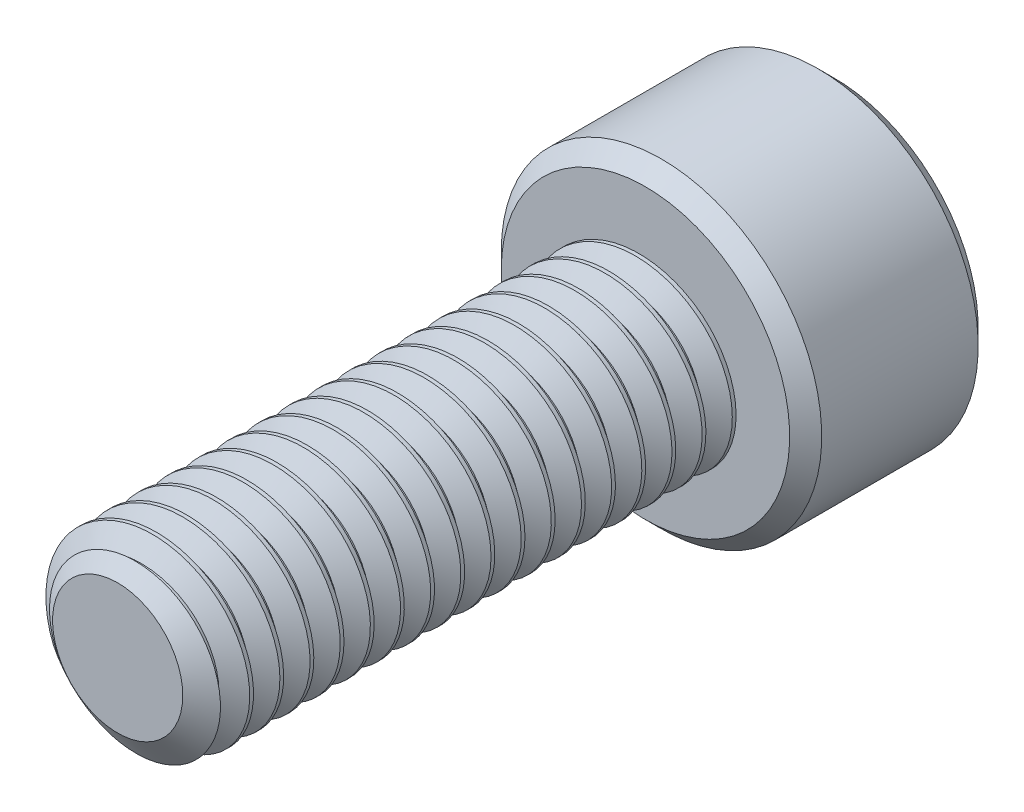
SolidWorks part; units mm, degrees
note: '?' marks a value the reader was unsure of.
other "DetailItem1"
ref_plane "Front Plane" through (0, 0, 0) normal (0, 0, 1) x (1, 0, 0)
ref_plane "Top Plane" through (0, 0, 0) normal (0, 1, 0) x (1, 0, 0)
ref_plane "Right Plane" through (0, 0, 0) normal (1, 0, 0) x (0, 0, -1)
sketch "Sketch1" plane through (0, 0, 0) normal (0, 0, 1) x (1, 0, 0)
  circle A0 centre (0, 0) radius 2.5
  dimension "OD" = 5
extrude "Extrude1" add sketch "Sketch1" against normal blind 14
sketch "Sketch2" plane through (0, 0, 0) normal (0, 0, 1) x (1, 0, 0)
  circle A0 centre (0, 0) radius 2.5 construction
  circle A1 centre (0, 0) radius 2.5
curve "Helix/Spiral1" pitch 0.8 height 14.8 turns 18.5 parameters "pitch"=0.8
sketch "Sketch3" plane through (0, 0, 0) normal (1, 0, 0) x (0, 0, -1)
  line L0 (-0.7, 2.5) -> (-0.4, 1.9804)
  line L1 (-0.4, 1.9804) -> (-0.3, 1.9804)
  line L2 (-0.3, 1.9804) -> (0, 2.5)
  line L3 (-0.7, 2.5) -> (0, 2.5)
  line L4 (-0.35, 2.5) -> (-0.35, 1.9804) construction
  line L5 (-0.55, 2.2402) -> (-0.15, 2.2402) construction
  line L6 (0, 2.5) -> (0, -2.5) construction
  dimension "D1" = 0.1
  dimension "D2" = 0.4
  dimension "D3" = 60
sweep "Cut-Sweep1" cut profiles "Sketch3" path "Helix/Spiral1"
sketch "Sketch4" plane through (0, 0, 0) normal (1, 0, 0) x (0, 0, -1)
  line L0 (0.5417, 2.5) -> (0, 1.7264)
  line L1 (0, 1.7264) -> (0, 2.5)
  line L2 (0.5417, 2.5) -> (0, 2.5)
  line L3 (-0.7, 2.5) -> (0, 2.5) construction
  line L4 (0, 0) -> (7.0209, 0) construction
  dimension "D1" = 55
  dimension "D2" = 0.254
revolve "Cut-Revolve1" cut sketch "Sketch4" angle 360 about L4
sketch "Sketch6" plane through (0, 0, -14) normal (0, 0, -1) x (-1, 0, 0)
  circle A0 centre (0, 0) radius 4.25
  dimension "head dia" = 8.5
extrude "Extrude2" add sketch "Sketch6" along normal blind 5
sketch "Sketch7" plane through (0, 0, -19) normal (0, 0, -1) x (-1, 0, 0)
  line L1 (0, 2.3094) -> (-2, 1.1547)
  line L2 (-2, 1.1547) -> (-2, -1.1547)
  line L3 (-2, -1.1547) -> (0, -2.3094)
  line L4 (0, -2.3094) -> (2, -1.1547)
  line L5 (2, -1.1547) -> (2, 1.1547)
  line L6 (2, 1.1547) -> (0, 2.3094)
  circle A0 centre (0, 0) radius 2 construction
  dimension "hex dia" = 4
extrude "Cut-Extrude1" cut sketch "Sketch7" against normal blind 3
sketch "Sketch8" plane through (0, 0, -19) normal (0, 0, -1) x (-1, 0, 0)
  circle A0 centre (0, 0) radius 2.3094
extrude "Cut-Extrude2" cut sketch "Sketch8" against normal through all draft 45
chamfer "Chamfer1" distance 0.425 angle 45 2 edges at (-4.25, 0, -19) (-4.25, 0, -14)
sketch "Sketch10" plane through (0, 0, -14) normal (0, 0, 1) x (1, 0, 0)
  circle A1 centre (0, 0) radius 2.5
  circle A2 centre (0, 0) radius 2.5
  dimension "D1" = 0
ref_plane "Plane1" through (0, 0, 0) normal (0, 0, 1) x (1, 0, 0)
extrude "partial thread" [suppressed] add sketch "Sketch10" along normal up to surface (13 mm away) separate body
chamfer "Chamfer2" [suppressed] distance 0.1 angle 45
combine bodies "Combine1" [suppressed] operation type? add bodies to combine 107 108
sketch "Sketch9" plane through (0, 0, 0) normal (1, 0, 0) x (0, 0, -1)
  line L0 (0, 2.5) -> (0, -2.5) construction
  line L1 (2, 2.5) -> (2, -2.5) construction
  dimension "D1" = 2
equation "\"D3@Helix/Spiral1\" = \"screw length@Extrude1\"+\"pitch@Helix/Spiral1\""
equation "\"D1@Sketch3\" = \"pitch@Helix/Spiral1\"*.125"
equation "\"D2@Sketch3\" = \"pitch@Helix/Spiral1\"*.5"
equation "\"D1@Cut-Extrude1\" = \"hex dia@Sketch7\"*.75"
equation "\"D1@Chamfer1\" = \"head dia@Sketch6\"*.05"
equation "\"D1@Sketch9\" = \"pitch@Helix/Spiral1\"*2.5"
equation "\"D1@Chamfer2\"=\"OD@Sketch1\"*.02"
